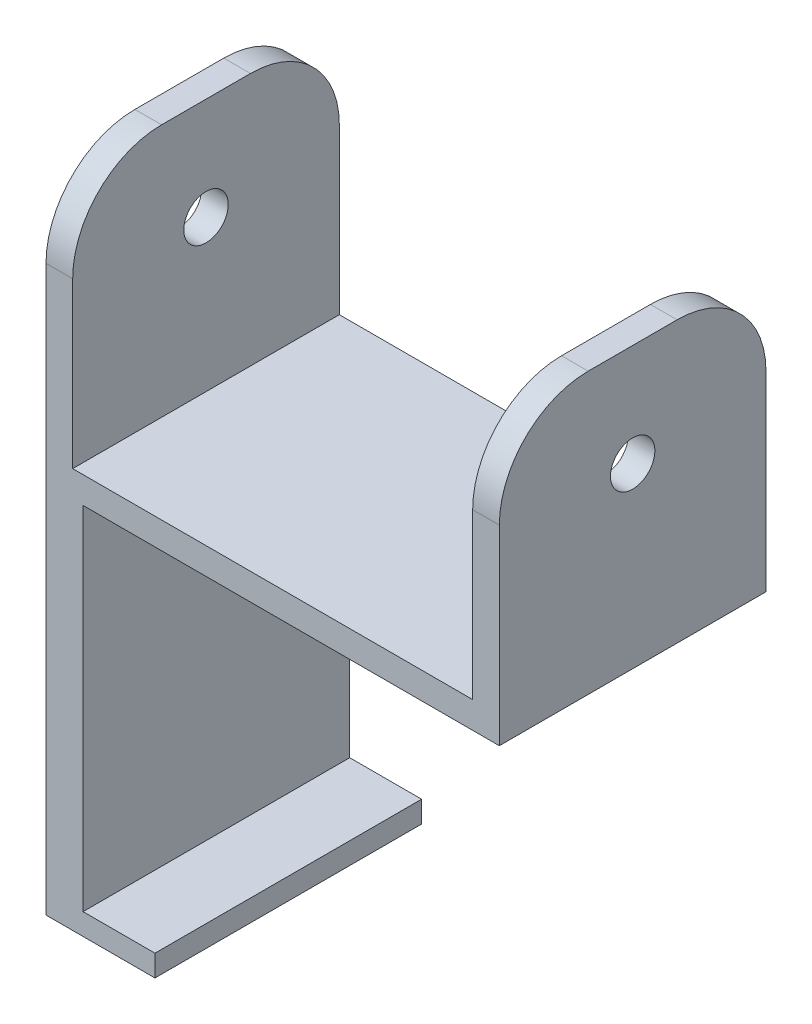
SolidWorks part; units mm, degrees
ref_plane "Front Plane" through (0, 0, 0) normal (0, 0, 1) x (1, 0, 0)
ref_plane "Top Plane" through (0, 0, 0) normal (0, 1, 0) x (1, 0, 0)
ref_plane "Right Plane" through (0, 0, 0) normal (1, 0, 0) x (0, 0, -1)
sketch "Sketch1" plane through (0, 0, 0) normal (0, 0, 1) x (1, 0, 0)
  line L0 (-21.8214, 30) -> (-21.8214, 0)
  line L1 (-21.8214, 0) -> (26.1786, 0)
  line L2 (26.1786, 0) -> (26.1786, 30)
  dimension "D1" = 48
  dimension "D2" = 30
extrude "Extrude-Thin1" add sketch "Sketch1" along normal mid plane 30 thin thin type mid plane wall 3
fillet "Fillet1" radius 10 4 edges at (26.1786, 30, 15) (26.1786, 30, -15) (-21.8214, 30, -15) (-21.8214, 30, 15)
sketch "Sketch2" plane through (27.6786, 0, 0) normal (1, 0, 0) x (0, 0, -1)
  line L0 (-15, -1.5) -> (15, -1.5) construction
  circle A0 centre (0, 18.5) radius 2.5
  dimension "D1" = 5
  dimension "D2" = 20
extrude "Cut-Extrude1" cut sketch "Sketch2" against normal blind 55
sketch "Sketch4" plane through (0, 0, -15) normal (0, 0, -1) x (-1, 0, 0)
  line L0 (23.3214, -1.5) -> (23.3214, -43.5)
  line L1 (23.3214, -43.5) -> (11.0651, -43.5)
  line L2 (11.0651, -43.5) -> (11.0651, -41.0796)
  line L3 (11.0651, -41.0796) -> (19.1532, -41.0796)
  line L4 (19.1532, -41.0796) -> (19.1532, -1.5)
  line L5 (23.3214, -1.5) -> (-27.6786, -1.5) construction
  line L6 (19.1532, -1.5) -> (23.3214, -1.5)
  dimension "D1" = 42
extrude "Boss-Extrude1" add sketch "Sketch4" against normal blind 30
